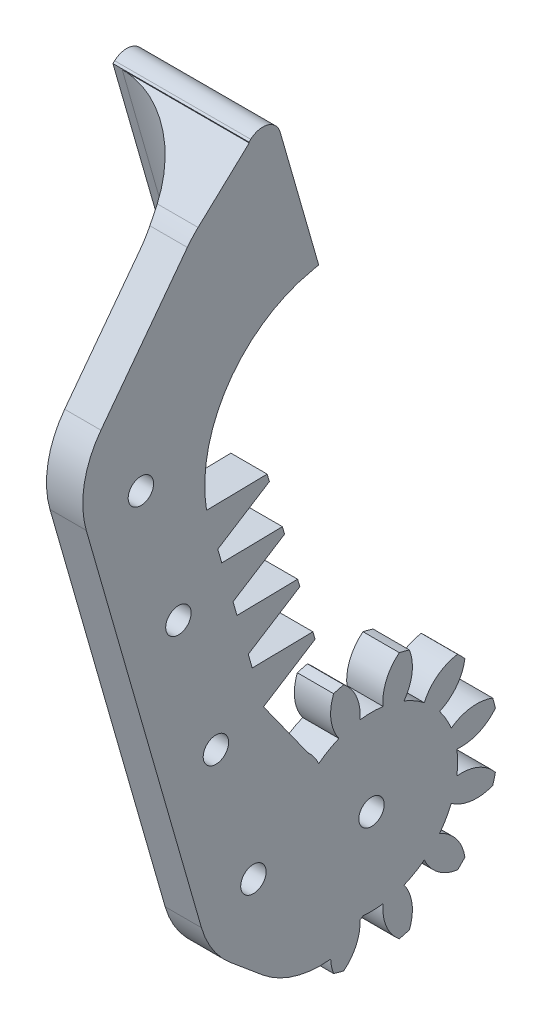
SolidWorks part; units mm, degrees
ref_plane "Plane1" through (0, 0, 0) normal (0, 0, 1) x (1, 0, 0)
ref_plane "Plane2" through (0, 0, 0) normal (0, 1, 0) x (1, 0, 0)
ref_plane "Plane3" through (0, 0, 0) normal (1, 0, 0) x (0, 0, -1)
other "Configuration Table"
sketch "HoldingSke" plane through (0, 0, 0) normal (0, 1, 0) x (1, 0, 0)
  line L0 (0, 0) -> (0.4891, -0.104)
  line L1 (-15, 0) -> (100, 0) construction
  line L2 (0, 0) -> (-2.1039, 2.3779)
  line L3 (0, 0) -> (-11.863, 4.5341)
  line L4 (0, 0) -> (8.4473, 1.7955)
  line L5 (0, 0) -> (-46.8476, -17.4728)
  line L6 (0, 0) -> (-3.3159, -2.2372)
  line L7 (-2.1039, 2.3779) -> (8.6586, 51.2059)
  line L8 (-76.2, 54.61) -> (-74.8, 54.61)
  line L9 (-67.7845, 28.3722) -> (-49.3413, 33.142)
  line L10 (-76.2, 71.12) -> (104.1128, 71.12)
  line L11 (0, 0) -> (-4, 0)
  line L12 (-76.2, 101.6) -> (-76.133, 101.6)
  line L13 (24.9733, 27.94) -> (52.9518, 28.4284)
  line L14 (24.9733, 27.94) -> (24.9743, 27.94)
  line L15 (24.9733, 27.94) -> (100.4006, 29.5858)
  line L16 (-63.627, -2) -> (-12.827, -2)
  circle A0 centre (0, 0) radius 4
  circle A1 centre (0, 0) radius 9.499
  circle A2 centre (0, 0) radius 37.5
  circle A3 centre (0, 0) radius 4
  dimension "Num_teeth" = 12
  dimension "Pitch_radius" = 180.3128
  dimension "Width" = 4
  dimension "Thickness" = 4
sketch "BasProSke" plane through (0, 0, 0) normal (0, 1, 0) x (1, 0, 0)
  line L0 (-10, 0) -> (60, 0) construction
  line L1 (0, 0) -> (0, 14)
  line L2 (0, 0) -> (4, 0)
  line L3 (4, 0) -> (4, 14)
  line L4 (4, 14) -> (0, 14)
  dimension "Thickness" = 4
  dimension "Diameter" = 28
revolve "Base-Revolve" add sketch "BasProSke" angle 360 about L0
sketch "TooCutSke" plane through (0, 0, 0) normal (1, 0, 0) x (0, 0, -1)
  line L1 (0, 0) -> (0, 107) construction
  line L2 (0, 0) -> (-1.6834, 11.8813) construction
  line L3 (0, 0) -> (-6.1662, 23.0126) construction
  line L4 (-1.6834, 11.8813) -> (-3.0831, 11.5063) construction
  arc A0 (1.2868, 9.4114) -> (-1.2868, 9.4114) centre (0, 0) ccw
  arc A1 (3.0888, 13.681) -> (-3.0888, 13.681) centre (0, 0) ccw
  circle A2 centre (0, 0) radius 12 construction
  circle A3 centre (0, 0) radius 11.6178 construction
  arc A4 (-1.2868, 9.4114) -> (-3.0888, 13.681) centre (-6.0607, 9.9117) ccw
  arc A5 (3.0888, 13.681) -> (1.2868, 9.4114) centre (6.0607, 9.9117) ccw
extrude "ToothCut" cut sketch "TooCutSke" along normal through all
fillet "Breaks" [suppressed] radius 0.04 tangent propagation no
fillet "RootFillets" [suppressed] radius 0.501
pattern_circular "TeethCuts" count 12 every 30 about axis through (-10, 0, 0) along (1, 0, 0) of "ToothCut", "RootFillets", "Breaks"
sketch "HubNeaOneSke" plane through (0, 0, 0) normal (-1, 0, 0) x (0, 0, 1)
  circle A0 centre (0, 0) radius 9.499
  dimension "Diameter" = 18.998
extrude "HubNearOne" [suppressed] add sketch "HubNeaOneSke" along normal blind 46.0001
sketch "HubNeaBotSke" plane through (0, 0, 0) normal (-1, 0, 0) x (0, 0, 1)
  circle A0 centre (0, 0) radius 9.499
  dimension "Diameter" = 18.998
extrude "HubNearBoth" [suppressed] add sketch "HubNeaBotSke" along normal blind 23
ref_plane "FarPln" through (4, 0, 0) normal (1, 0, 0) x (0, 0, -1)
sketch "HubFarSke" plane through (4, 0, 0) normal (1, 0, 0) x (0, 0, -1)
  circle A0 centre (0, 0) radius 9.499
  dimension "Diameter" = 18.998
extrude "HubFar" [suppressed] add sketch "HubFarSke" along normal blind 23
sketch "BorSke" plane through (0, 0, 0) normal (1, 0, 0) x (0, 0, -1)
  circle A0 centre (0, 0) radius 4
  dimension "Diameter" = 8
extrude "Bore" cut sketch "BorSke" along normal mid plane 100.0001
sketch "KeySke" plane through (0, 0, 0) normal (1, 0, 0) x (0, 0, -1)
  line L0 (-1.5, 0) -> (-1.5, 5.4)
  line L1 (-1.5, 5.4) -> (1.5, 5.4)
  line L2 (1.5, 5.4) -> (1.5, 0)
  line L3 (0, 0) -> (0, 34) construction
  line L4 (-1.5, 0) -> (1.5, 0)
  dimension "Width" = 3
extrude "Keyway" [suppressed] cut sketch "KeySke" along normal mid plane 100.0001
pattern_circular "Keyway2" [suppressed] count 2 every 90 about axis through (-10, 0, 0) along (1, 0, 0) reverse direction yes
sketch "草图3" plane through (4, 0, 0) normal (1, 0, 0) x (0, 0, -1)
  line L0 (-0.9328, -9.484) -> (-7.2201, -13.5851)
  line L1 (-7.2201, -13.5851) -> (-17.904, -4.6421)
  line L2 (-17.904, -4.6421) -> (-27.1078, 27.4555)
  line L3 (-27.1078, 27.4555) -> (-31.2747, 41.9872)
  line L4 (-31.2747, 41.9872) -> (-32.8188, 47.3719)
  line L5 (-32.8188, 47.3719) -> (-19.7697, 64.7465)
  line L6 (9.499, 0) -> (9.499, 73.2106) construction
  line L7 (-19.7697, 64.7465) -> (-10.9531, 72.9519)
  line L15 (-10.9531, 72.9519) -> (-6.1261, 56.1182)
  line L16 (-6.1261, 56.1182) -> (-5.8367, 55.1089)
  line L17 (-18.1887, 37.8763) -> (-11.5021, 37.9923)
  line L18 (-11.5021, 37.9923) -> (-11.262, 37.1552)
  line L19 (-11.262, 37.1552) -> (-16.9478, 33.5489)
  line L20 (-16.509, 32.0186) -> (-9.8224, 32.1346)
  line L21 (-9.5823, 31.2975) -> (-15.2681, 27.6912)
  line L22 (-9.8224, 32.1346) -> (-9.5823, 31.2975)
  line L23 (-14.8293, 26.1609) -> (-8.1427, 26.2769)
  line L24 (-7.9027, 25.4398) -> (-13.5885, 21.8335)
  line L25 (-8.1427, 26.2769) -> (-7.9027, 25.4398)
  line L26 (-13.1497, 20.3032) -> (-6.4631, 20.4193)
  line L27 (-6.223, 19.5821) -> (-11.9088, 15.9758)
  line L28 (-6.4631, 20.4193) -> (-6.223, 19.5821)
  line L29 (-16.9478, 33.5489) -> (-16.509, 32.0186)
  line L30 (-15.2681, 27.6912) -> (-14.8293, 26.1609)
  line L31 (-13.5885, 21.8335) -> (-13.1497, 20.3032)
  line L32 (-11.9088, 15.9758) -> (-5.7807, 7.4225)
  arc A0 (9.4114, -1.2868) -> (9.4114, 1.2868) centre (0, 0) ccw construction
  arc A1 (-5.7807, 7.4225) -> (-0.9328, -9.484) centre (34.7107, 9.8849) ccw
  arc A3 (-18.1887, 37.8763) -> (-5.8367, 55.1089) centre (-3.3963, 40.3166) cw
  dimension "D1" = 4
extrude "凸台-拉伸1" add sketch "草图3" against normal blind 4
fillet "圆角1" radius 10 4 edges at (2, 47.3719, 32.8188) (2, 64.7465, 19.7697) (2, -4.6421, 17.904) (2, -13.5851, 7.2201)
sketch "草图4" plane through (4, 0, 0) normal (1, 0, 0) x (0, 0, -1)
  line L0 (-10.9452, 72.9813) -> (-5.8288, 55.1383)
  line L1 (-10.9452, 72.9813) -> (-13.512, 70.7001)
  line L3 (-13.512, 70.7001) -> (-8.8288, 54.3676)
  line L4 (-13.512, 70.7001) -> (-10.9452, 72.9813)
  line L5 (-8.8288, 54.3676) -> (-5.8288, 55.1383)
  dimension "D1" = 3
extrude "凸台-拉伸2" add sketch "草图4" against normal blind 15 contours L3 L5 L0 L1 region at (4, 63.308, 9.7582)
fillet "圆角2" radius 2 1 edges at (-3.5, 72.9813, 10.9452)
fillet "圆角3" radius 10 1 edges at (0, 62.4827, 11.1557)
sketch "草图6" plane through (0, 0, 0) normal (-1, 0, 0) x (0, 0, 1)
  circle A0 centre (0, 0) radius 4
  circle A1 centre (0, 0) radius 1.4
extrude "凸台-拉伸3" add sketch "草图6" against normal blind 4
sketch "草图7" plane through (0, 2.6405, -9.2084) normal (0, 0.2756, -0.9613) x (-1, 0, 0)
  line L0 (11, 69.9933) -> (11, 54.6089) construction
  line L1 (11, 54.6089) -> (-4, 54.6089) construction
  circle A0 centre (4, 62.6089) radius 1.4
  dimension "D3" = 2.8
  dimension "D1" = 7
  dimension "D2" = 8
extrude "切除-拉伸6" cut sketch "草图7" along normal blind 15 and the other way blind 34
sketch "草图8" plane through (0, 1.7914, -6.2472) normal (0, -0.2756, 0.9613) x (1, 0, 0)
  circle A0 centre (-4, 62.6089) radius 3
extrude "切除-拉伸7" cut sketch "草图8" along normal blind 6
sketch "草图10" plane through (4, 0, 0) normal (1, 0, 0) x (0, 0, -1)
  line L0 (-31.4473, 42.5889) -> (-18.7485, -1.6969) construction
  circle A0 centre (-25.4239, 43.3506) radius 1.4
  circle A1 centre (-21.2893, 28.9317) radius 1.4
  circle A2 centre (-17.1548, 14.5127) radius 1.4
  circle A3 centre (-13.0202, 0.0938) radius 1.4
  dimension "D1" = 6
  dimension "D2" = 6
  dimension "D3" = 6
  dimension "D4" = 6
  dimension "D5" = 15
  dimension "D6" = 15
  dimension "D7" = 15
  dimension "D8" = 8
extrude "切除-拉伸8" cut sketch "草图10" against normal blind 15 contours A3 | A0 | A2 | A1
equation "' \"Module@HoldingSke\" = 6.35"
equation "' \"Num_teeth@HoldingSke\" = 12"
equation "' \"Ap@HoldingSke\" =  20"
equation "' \"Ap@HoldingSke\" = 20"
equation "' \"Width@HoldingSke\" = 0.5 * 25.4"
equation "' \"Hub_dia@HoldingSke\"= 1 * 25.4"
equation "' \"Hub_dia@HoldingSke\" = 1 * 25.4"
equation "' \"Overall_len@HoldingSke\" = 1.0 * 25.4"
equation "' \"Bore@HoldingSke\" = 0.75 * 25.4"
equation "' \"T_dim@HoldingSke\" = 0.1 * 25.4"
equation "' \"Width@KeySke\" = 0.25 * 25.4"
equation "' \"Show_teeth@HoldingSke\" = 13"
equation "' \"Backlash@HoldingSke\" = 0.009 * 25.4"
equation "' \"Addendum_fac@HoldingSke\" = 1.0"
equation "' \"Dedendum_fac@HoldingSke\" = 1.25"
equation "' \"Dedendum_add@HoldingSke\" = 0.00005 * 25.4"
equation "' \"Clearance_fac@HoldingSke\" = 0.25"
equation "\"Pitch@HoldingSke\" = 1 / \"Module@HoldingSke\""
equation "\"Overcut_dia@TooCutSke\" = (\"Num_teeth@HoldingSke\" + 2 * \"Addendum_fac@HoldingSke\") / \"Pitch@HoldingSke\" + 0.002 * 25.4"
equation "\"Pitch_dia@TooCutSke\" = \"Num_teeth@HoldingSke\" / \"Pitch@HoldingSke\""
equation "\"Base_dia@TooCutSke\" = \"Num_teeth@HoldingSke\" / \"Pitch@HoldingSke\" * cos((\"Ap@HoldingSke\"  * 3.14159265 / 180))"
equation "\"Root_dia@TooCutSke\" = (\"Num_teeth@HoldingSke\" + 2) / \"Pitch@HoldingSke\" - 2 * (\"Addendum_fac@HoldingSke\" + \"Dedendum_fac@HoldingSke\") / \"Pitch@HoldingSke\" - \"Dedendum_add@HoldingSke\" * 2"
equation "\"Half_ang@TooCutSke\" = 180 / \"Num_teeth@HoldingSke\""
equation "\"Half_CT@TooCutSke\" = \"Num_teeth@HoldingSke\" / \"Pitch@HoldingSke\" * sin((3.14159265 / 2 / \"Num_teeth@HoldingSke\")) / 2 - 7 * \"Backlash@HoldingSke\" / 4"
equation "\"Flank_rad@TooCutSke\" = \"Num_teeth@HoldingSke\" / \"Pitch@HoldingSke\" / 5"
equation "\"Radius@RootFillets\" = \"Clearance_fac@HoldingSke\" / \"Pitch@HoldingSke\" + \"Dedendum_add@HoldingSke\""
equation "\"Break_rad@Breaks\" = 0.02 / \"Pitch@HoldingSke\""
equation "\"Thickness@HoldingSke\" = \"Width@HoldingSke\""
equation "\"OAL@HoldingSke\" = \"Thickness@HoldingSke\""
equation "\"MHD@HoldingSke\" = (\"Num_teeth@HoldingSke\" + 2) / \"Pitch@HoldingSke\" - 2 * (\"Addendum_fac@HoldingSke\" + \"Dedendum_fac@HoldingSke\")  / \"Pitch@HoldingSke\" - \"Dedendum_add@HoldingSke\" * 2"
equation "\"MBD@HoldingSke\" = (\"Num_teeth@HoldingSke\" + 2) / \"Pitch@HoldingSke\" - 2 * (\"Addendum_fac@HoldingSke\" + \"Dedendum_fac@HoldingSke\")  / \"Pitch@HoldingSke\" - \"Dedendum_add@HoldingSke\" * 2 - 0.002 * 25.4"
equation "\"MHD@HoldingSke\" = ((sgn( \"MHD@HoldingSke\" - \"Hub_dia@HoldingSke\" )-1)*( \"MHD@HoldingSke\" - \"Hub_dia@HoldingSke\" ))/-2+ \"Hub_dia@HoldingSke\""
equation "\"MBD@HoldingSke\" = ((sgn( \"MBD@HoldingSke\" - \"Bore@HoldingSke\" )-1)*( \"MBD@HoldingSke\" - \"Bore@HoldingSke\" ))/-2+ \"Bore@HoldingSke\""
equation "\"OAL@HoldingSke\" = ((sgn( \"OAL@HoldingSke\" - \"Overall_len@HoldingSke\" )+1)*( \"OAL@HoldingSke\" - \"Overall_len@HoldingSke\" ))/2 + \"Overall_len@HoldingSke\" + 0.000002 * 25.4"
equation "\"Num_teeth@TeethCuts\" = int( \"Show_teeth@HoldingSke\" ) + 1"
equation "\"Num_teeth@TeethCuts\" = ((sgn( \"Num_teeth@TeethCuts\" - \"Num_teeth@HoldingSke\" )-1)*( \"Num_teeth@TeethCuts\" - \"Num_teeth@HoldingSke\" ))/-2+ \"Num_teeth@HoldingSke\""
equation "\"Num_teeth@TeethCuts\" = ((sgn( \"Num_teeth@TeethCuts\" - 2.0)+1)*( \"Num_teeth@TeethCuts\" - 2.0))/2 +2.0"
equation "\"Angle@TeethCuts\" = 360.0 / \"Num_teeth@HoldingSke\""
equation "\"Diameter@BasProSke\" = (\"Num_teeth@HoldingSke\" + 2 * \"Addendum_fac@HoldingSke\") / \"Pitch@HoldingSke\""
equation "\"Thickness@BasProSke\"  = \"Thickness@HoldingSke\""
equation "' \"Fillet_rad@BasProSke\" =  \"Thickness@HoldingSke\" * 0.05"
equation "' \"Fillet_rad@BasProSke\" = \"Thickness@HoldingSke\" * 0.05"
equation "\"MHD@HoldingSke\" = ((sgn( \"MHD@HoldingSke\" - \"Root_dia@TooCutSke\" )-1)*( \"MHD@HoldingSke\" - \"Root_dia@TooCutSke\" ))/-2+ \"Root_dia@TooCutSke\""
equation "\"Diameter@HubNeaOneSke\" = \"MHD@HoldingSke\""
equation "\"Length@HubNearOne\" = \"OAL@HoldingSke\" - \"Thickness@BasProSke\""
equation "\"Diameter@HubNeaBotSke\" = \"MHD@HoldingSke\""
equation "\"Length@HubNearBoth\" = ( \"OAL@HoldingSke\" - \"Thickness@BasProSke\" ) / 2.0"
equation "\"Thickness@FarPln\" = \"Thickness@BasProSke\""
equation "\"Diameter@HubFarSke\" = \"MHD@HoldingSke\""
equation "\"Length@HubFar\" = ( \"OAL@HoldingSke\" - \"Thickness@BasProSke\" ) / 2.0"
equation "\"Diameter@BorSke\" = \"MBD@HoldingSke\""
equation "\"D1@Bore\" = \"OAL@HoldingSke\" * 2.0"
equation "\"D1@Keyway\" = \"OAL@HoldingSke\" * 2.0"
equation "\"Offset@KeySke\" = \"T_dim@HoldingSke\" + \"MBD@HoldingSke\" / 2.0"
